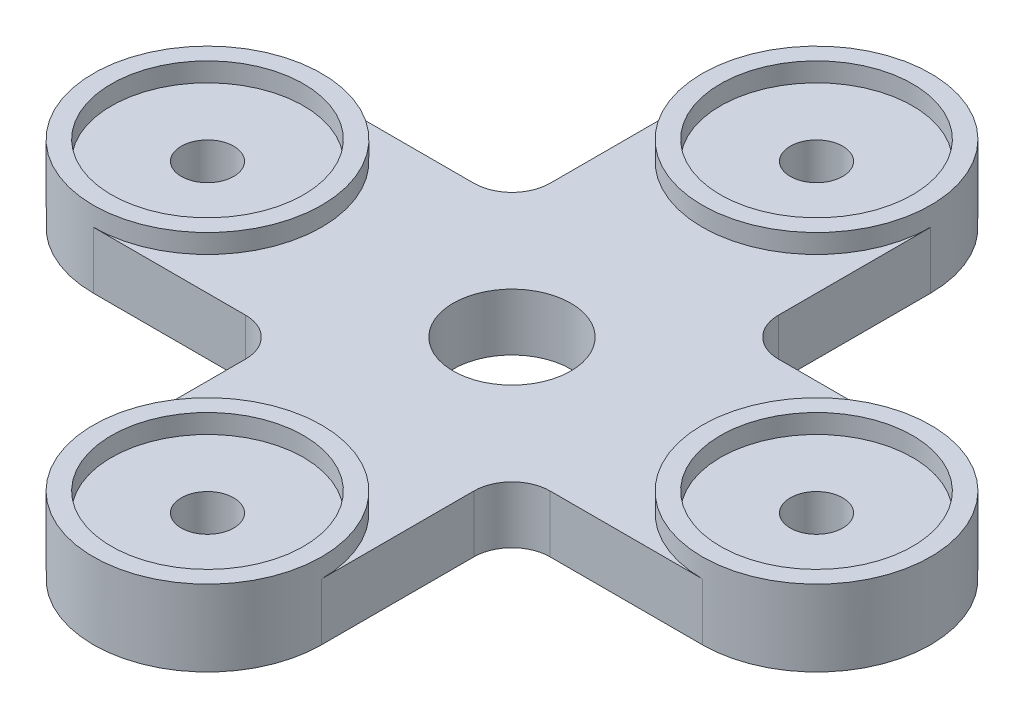
SolidWorks part; units mm, degrees
ref_plane "Front Plane" through (0, 0, 0) normal (0, 0, 1) x (1, 0, 0)
ref_plane "Top Plane" through (0, 0, 0) normal (0, 1, 0) x (1, 0, 0)
ref_plane "Right Plane" through (0, 0, 0) normal (1, 0, 0) x (0, 0, -1)
sketch "Sketch1" plane through (0, 0, 0) normal (0, 1, 0) x (1, 0, 0)
  line L0 (0, 0) -> (0, 20.32) construction
  line L1 (7.62, 20.32) -> (7.62, 6.8928)
  line L3 (-7.62, 20.32) -> (-7.62, 6.8928)
  circle A0 centre (0, 0) radius 20.32 construction
  circle A2 centre (0, 0) radius 3.925
  circle A4 centre (0, 0) radius 10.275
  arc A8 (7.62, 20.32) -> (-7.62, 20.32) centre (0, 20.32) ccw
  circle A9 centre (0, 20.32) radius 6.4135
  circle A10 centre (0, 20.32) radius 7.62
  point P11 (0, 20.32)
  dimension "D1" = 20.32
  dimension "D2" = 7.62
  dimension "D3" = 7.85
  dimension "D4" = 6.35
  dimension "D5" = 12.827
extrude "Boss-Extrude1" add sketch "Sketch1" along normal blind 3.81 contours A4 | A4 A2 | A10 region at (0, 0, -11.9749) region at (9.3171, 0, -3.5888)
extrude "Boss-Extrude2" add sketch "Sketch1<3>" along normal blind 5.08 contours A8 A10 A9 region at (0, 0, -12.9155)
sketch "Sketch1<3>" plane through (0, 0, 0) normal (0, 1, 0) x (1, 0, 0) same geometry as "Sketch1"
hole_wizard "#5 (0.13779528) Diameter Hole1" positions "Sketch5" profile "Sketch6" hole size "#5" standard "ANSI Inch" end condition through all
sketch "Sketch5" plane through (0, 3.81, 0) normal (0, 1, 0) x (1, 0, 0)
  point P0 (0, 20.32)
sketch "Sketch6" plane through (0, 3.81, -20.32) normal (1, 0, 0) x (0, 0, 1)
  line L0 (0, 0) -> (0, 3.81)
  line L1 (0, 3.81) -> (1.75, 3.81)
  line L2 (1.75, 3.81) -> (1.75, 0)
  line L5 (1.75, 0) -> (0, 0)
  line L11 (0, -6.35) -> (0, 107.95) construction
  dimension "Thru Hole Dia." = 3.5
  dimension "Thru Hole Depth" = 3.81
pattern_circular "CirPattern1" count 4 over 360 about axis through (0, 3.81, 0) along (0, 1, 0) of "Boss-Extrude1", "#5 (0.13779528) Diameter Hole1", "Boss-Extrude2"
fillet "Fillet1" radius 2.54 4 edges at (-7.62, 1.905, -7.62) (7.62, 1.905, -7.62) (-7.62, 1.905, 7.62) (7.62, 1.905, 7.62)
